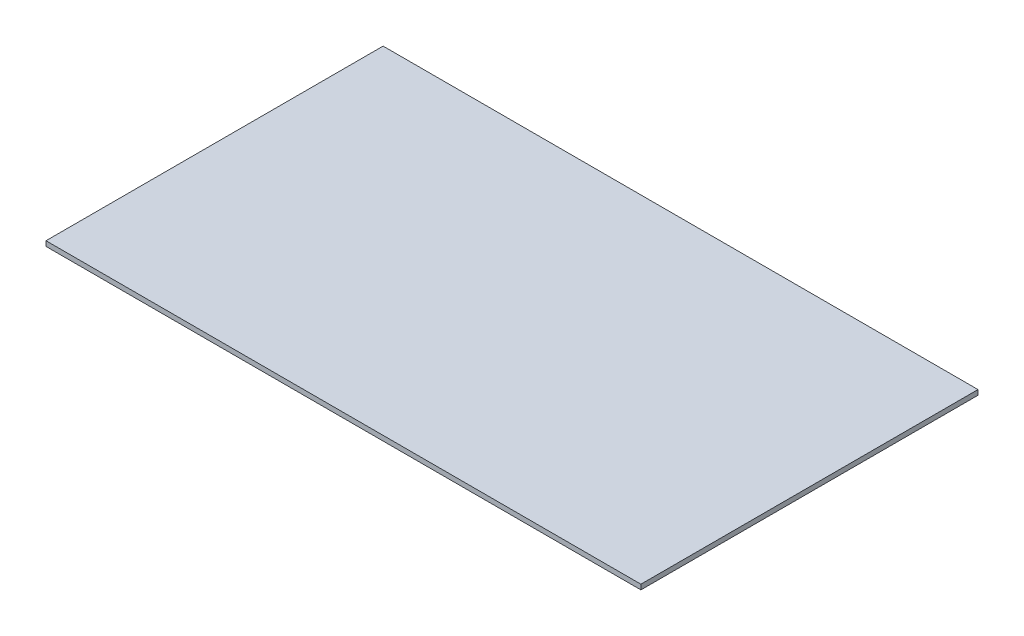
SolidWorks part; units mm, degrees
ref_plane "Front Plane" through (0, 0, 0) normal (0, 0, 1) x (1, 0, 0)
ref_plane "Top Plane" through (0, 0, 0) normal (0, 1, 0) x (1, 0, 0)
ref_plane "Right Plane" through (0, 0, 0) normal (1, 0, 0) x (0, 0, -1)
sketch "Sketch1" plane through (0, 0, 0) normal (0, 1, 0) x (1, 0, 0)
  line L7 (0, 0) -> (762, 0)
  line L8 (0, 0) -> (0, 431.8)
  line L9 (0, 431.8) -> (762, 431.8)
  line L10 (762, 0) -> (762, 431.8)
  dimension "D1" = 762
  dimension "D2" = 431.8
extrude "Boss-Extrude1" add sketch "Sketch1" along normal blind 6.35
